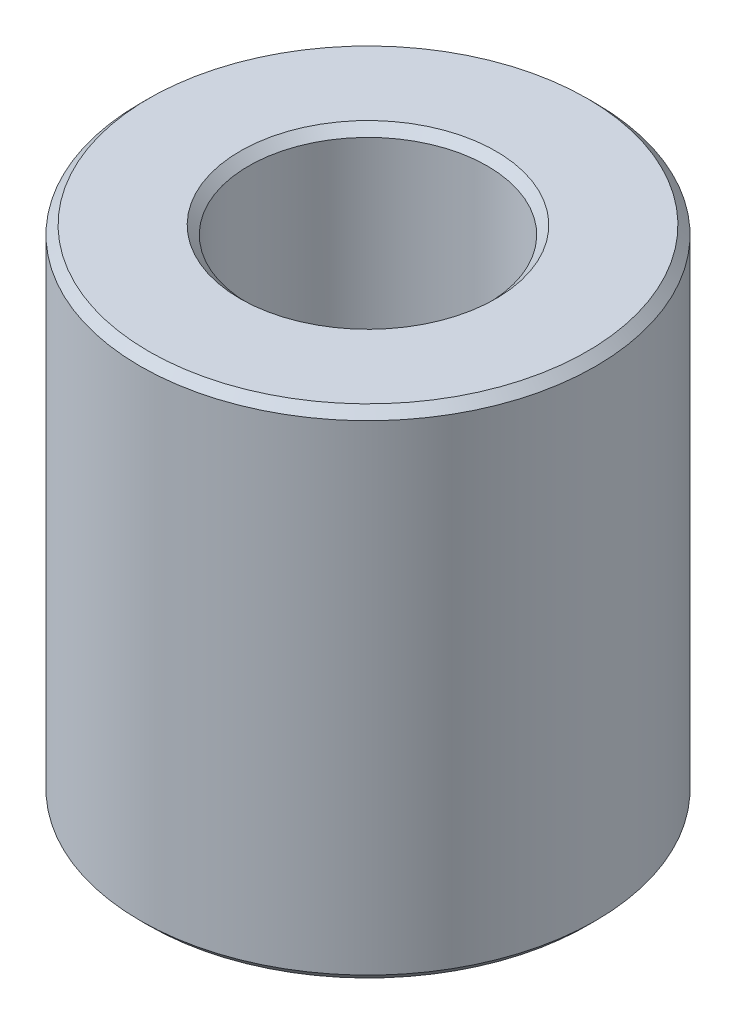
SolidWorks part; units mm, degrees
ref_plane "Front Plane" through (0, 0, 0) normal (0, 0, 1) x (1, 0, 0)
ref_plane "Top Plane" through (0, 0, 0) normal (0, 1, 0) x (1, 0, 0)
ref_plane "Right Plane" through (0, 0, 0) normal (1, 0, 0) x (0, 0, -1)
sketch "Sketch1" plane through (0, 0, 0) normal (0, 1, 0) x (1, 0, 0)
  circle A0 centre (0, 0) radius 47.5
  dimension "SLEEVE_OD" = 95
extrude "Boss-Extrude1" add sketch "Sketch1" along normal blind 103.716
sketch "Sketch2" plane through (0, 0, 0) normal (0, 1, 0) x (1, 0, 0)
  circle A0 centre (0, 0) radius 24.8876
  dimension "BORE_D" = 49.7751
extrude "Cut-Extrude1" cut sketch "Sketch2" along normal through all
chamfer "Chamfer1" distance 1.7848 angle 45 4 edges at (0, 103.716, 24.8876) (0, 0, 24.8876) (0, 0, 47.5) (0, 103.716, 47.5)
